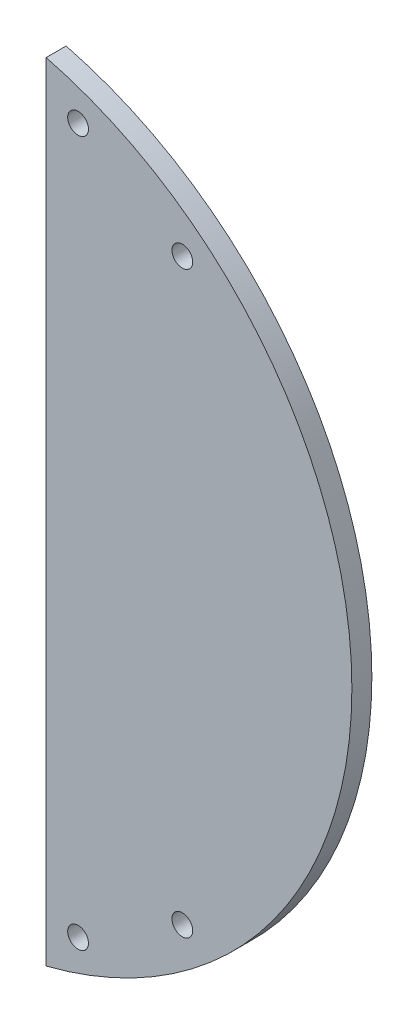
SolidWorks part; units mm, degrees
ref_plane "Front Plane" through (0, 0, 0) normal (0, 0, 1) x (1, 0, 0)
ref_plane "Top Plane" through (0, 0, 0) normal (0, 1, 0) x (1, 0, 0)
ref_plane "Right Plane" through (0, 0, 0) normal (1, 0, 0) x (0, 0, -1)
sketch "Sketch1" plane through (0, 0, 0) normal (0, 0, 1) x (-1, 0, 0)
  line L3 (0, -62.1367) -> (0, 62.8696)
  circle A15 centre (-5.075, 56.3664) radius 1.65
  circle A16 centre (-21.6385, 46.3664) radius 1.65
  circle A21 centre (-5.075, -55.6336) radius 1.65
  circle A22 centre (-21.6385, -45.6336) radius 1.65
  arc A23 (0, 62.8696) -> (0, -62.1367) centre (15.925, 0.3664) ccw
  point P2 (15.925, 0.3664)
  dimension "D10" = 3.3
  dimension "D2" = 64.5
extrude "Boss-Extrude1" add sketch "Sketch1" along normal blind 3.175
